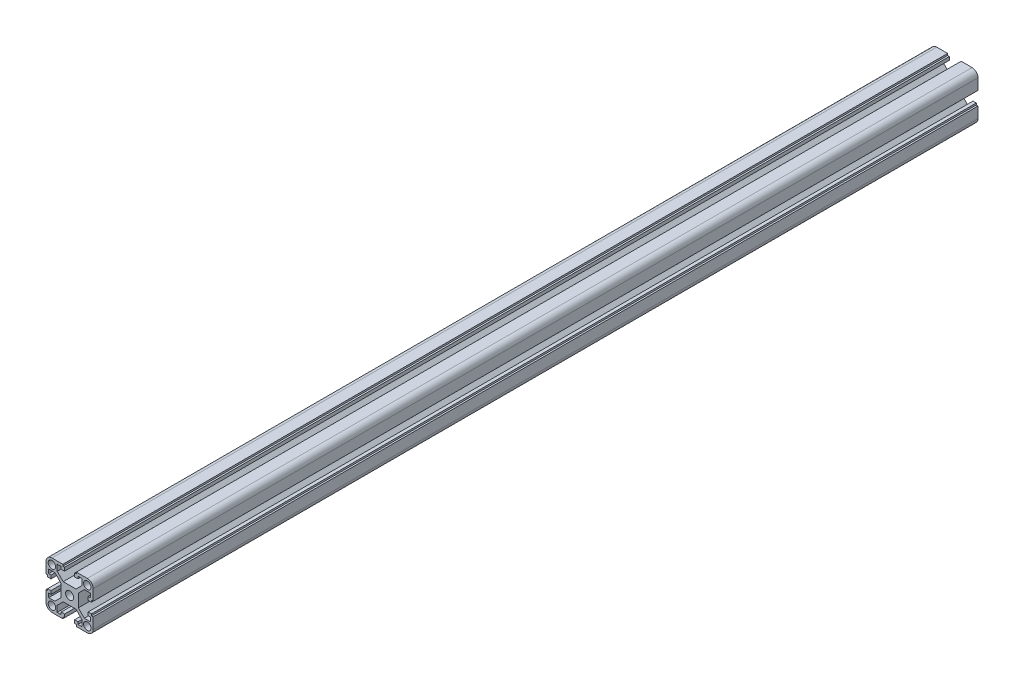
SolidWorks part; units mm, degrees
material "АД1 ГОСТ 4784-97"
ref_plane "Спереди" through (0, 0, 0) normal (0, 0, 1) x (1, 0, 0)
ref_plane "Сверху" through (0, 0, 0) normal (0, 1, 0) x (1, 0, 0)
ref_plane "Справа" through (0, 0, 0) normal (1, 0, 0) x (0, 0, -1)
ref_axis "ОсьX" through (-88.99, 0, 0) along (1, 0, 0)
ref_axis "ОсьZ" through (0, 55, 0) along (0, -1, 0)
ref_axis "ОсьY" through (0, 0, -88.99) along (0, 0, 1)
sketch "Эскиз1" plane through (0, 0, 0) normal (0, 0, 1) x (1, 0, 0)
  line L0 (-15, 20) -> (-5.7274, 20)
  line L1 (-5.7274, 20) -> (-5.7274, 18.5304)
  line L2 (-5.7274, 18.5304) -> (-4.25, 18.5304)
  line L3 (-4.25, 18.5304) -> (-4.25, 15.732)
  line L4 (-4.25, 15.732) -> (-7.1118, 15.732)
  line L5 (-7.1118, 15.732) -> (-7.1118, 17.7)
  line L6 (-7.1118, 17.7) -> (-10.5, 17.7)
  line L7 (-10.5, 17.7) -> (-10.5, 12.4799)
  line L8 (-10.5, 12.4799) -> (-5.4201, 7.4)
  line L9 (-20, 15) -> (-20, 5.7274)
  line L10 (0, 0) -> (0, 8.4096) construction
  line L11 (-15, 15) -> (0, 0) construction
  line L12 (10.5, 12.4799) -> (5.4201, 7.4)
  line L13 (10.5, 17.7) -> (10.5, 12.4799)
  line L14 (7.1118, 17.7) -> (10.5, 17.7)
  line L15 (7.1118, 15.732) -> (7.1118, 17.7)
  line L16 (4.25, 15.732) -> (7.1118, 15.732)
  line L17 (4.25, 18.5304) -> (4.25, 15.732)
  line L18 (5.7274, 18.5304) -> (4.25, 18.5304)
  line L19 (5.7274, 20) -> (5.7274, 18.5304)
  line L20 (15, 20) -> (5.7274, 20)
  line L21 (-5.4201, 7.4) -> (5.4201, 7.4)
  line L22 (-8.8445, 0) -> (0, 0) construction
  line L23 (-12.4799, 10.5) -> (-7.4, 5.4201)
  line L24 (-17.7, 10.5) -> (-12.4799, 10.5)
  line L25 (-17.7, 7.1118) -> (-17.7, 10.5)
  line L26 (-15.732, 7.1118) -> (-17.7, 7.1118)
  line L27 (-15.732, 4.25) -> (-15.732, 7.1118)
  line L28 (-18.5304, 4.25) -> (-15.732, 4.25)
  line L29 (-18.5304, 5.7274) -> (-18.5304, 4.25)
  line L30 (-20, 5.7274) -> (-18.5304, 5.7274)
  line L31 (18.5304, 5.7274) -> (18.5304, 4.25)
  line L32 (18.5304, 4.25) -> (15.732, 4.25)
  line L33 (15.732, 4.25) -> (15.732, 7.1118)
  line L34 (15.732, 7.1118) -> (17.7, 7.1118)
  line L35 (12.4799, 10.5) -> (7.4, 5.4201)
  line L36 (17.7, 10.5) -> (12.4799, 10.5)
  line L37 (17.7, 7.1118) -> (17.7, 10.5)
  line L38 (20, 5.7274) -> (18.5304, 5.7274)
  line L39 (20, 15) -> (20, 5.7274)
  line L40 (20, -15) -> (20, -5.7274)
  line L41 (20, -5.7274) -> (18.5304, -5.7274)
  line L42 (17.7, -7.1118) -> (17.7, -10.5)
  line L43 (17.7, -10.5) -> (12.4799, -10.5)
  line L44 (12.4799, -10.5) -> (7.4, -5.4201)
  line L45 (15.732, -7.1118) -> (17.7, -7.1118)
  line L46 (15.732, -4.25) -> (15.732, -7.1118)
  line L47 (18.5304, -4.25) -> (15.732, -4.25)
  line L48 (18.5304, -5.7274) -> (18.5304, -4.25)
  line L49 (-20, -5.7274) -> (-18.5304, -5.7274)
  line L50 (-18.5304, -5.7274) -> (-18.5304, -4.25)
  line L51 (-18.5304, -4.25) -> (-15.732, -4.25)
  line L52 (-15.732, -4.25) -> (-15.732, -7.1118)
  line L53 (-15.732, -7.1118) -> (-17.7, -7.1118)
  line L54 (-17.7, -7.1118) -> (-17.7, -10.5)
  line L55 (-17.7, -10.5) -> (-12.4799, -10.5)
  line L56 (-12.4799, -10.5) -> (-7.4, -5.4201)
  line L57 (-5.4201, -7.4) -> (5.4201, -7.4)
  line L58 (15, -20) -> (5.7274, -20)
  line L59 (5.7274, -20) -> (5.7274, -18.5304)
  line L60 (5.7274, -18.5304) -> (4.25, -18.5304)
  line L61 (4.25, -18.5304) -> (4.25, -15.732)
  line L62 (4.25, -15.732) -> (7.1118, -15.732)
  line L63 (7.1118, -15.732) -> (7.1118, -17.7)
  line L64 (7.1118, -17.7) -> (10.5, -17.7)
  line L65 (10.5, -17.7) -> (10.5, -12.4799)
  line L66 (10.5, -12.4799) -> (5.4201, -7.4)
  line L67 (-20, -15) -> (-20, -5.7274)
  line L68 (-10.5, -12.4799) -> (-5.4201, -7.4)
  line L69 (-10.5, -17.7) -> (-10.5, -12.4799)
  line L70 (-7.1118, -17.7) -> (-10.5, -17.7)
  line L71 (-7.1118, -15.732) -> (-7.1118, -17.7)
  line L72 (-4.25, -15.732) -> (-7.1118, -15.732)
  line L73 (-4.25, -18.5304) -> (-4.25, -15.732)
  line L74 (-5.7274, -18.5304) -> (-4.25, -18.5304)
  line L75 (-5.7274, -20) -> (-5.7274, -18.5304)
  line L76 (-15, -20) -> (-5.7274, -20)
  line L77 (-7.4, 5.4201) -> (-7.4, -5.4201)
  line L78 (7.4, 5.4201) -> (7.4, -5.4201)
  circle A0 centre (0, 0) radius 3.4
  circle A1 centre (-15, 15) radius 3.15
  arc A2 (-15, 20) -> (-20, 15) centre (-15, 15) ccw
  arc A3 (15, 20) -> (20, 15) centre (15, 15) cw
  circle A4 centre (15, 15) radius 3.15
  circle A5 centre (15, -15) radius 3.15
  arc A6 (15, -20) -> (20, -15) centre (15, -15) ccw
  arc A7 (-15, -20) -> (-20, -15) centre (-15, -15) cw
  circle A8 centre (-15, -15) radius 3.15
  dimension "D1" = 6.8
  dimension "D2" = 6.3
  dimension "D3" = 40
  dimension "D8" = 30
  dimension "D4" = 2.3
  dimension "D5" = 1.35
  dimension "D6" = 21
  dimension "D7" = 8.5
  dimension "D9" = 45
  dimension "D10" = 2.8
  dimension "D11" = 4
  dimension "D13" = 40
extrude "Бобышка-Вытянуть1" add sketch "Эскиз1" along normal mid plane 750
